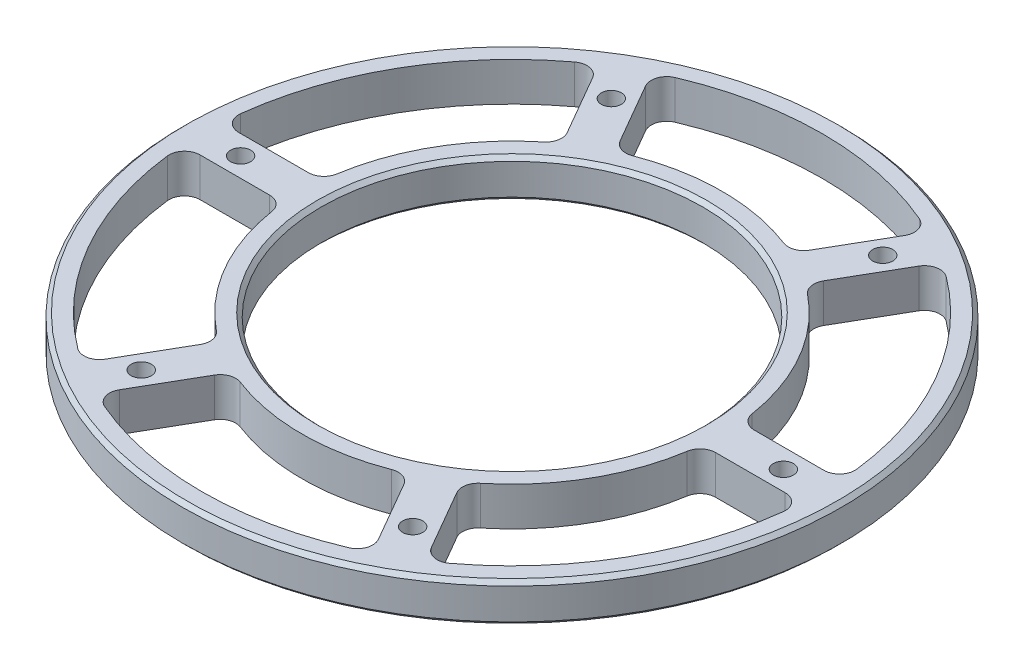
SolidWorks part; units mm, degrees
ref_plane "Front Plane" through (0, 0, 0) normal (0, 0, 1) x (1, 0, 0)
ref_plane "Top Plane" through (0, 0, 0) normal (0, 1, 0) x (1, 0, 0)
ref_plane "Right Plane" through (0, 0, 0) normal (1, 0, 0) x (0, 0, -1)
sketch "Sketch2" plane through (0, 0, 0) normal (1, 0, 0) x (0, 0, -1)
  line L0 (-49.2125, 0) -> (-84.9998, 0)
  line L1 (-84.9998, 0) -> (-84.9998, 10)
  line L2 (-84.9998, 10) -> (-49.2125, 10)
  line L3 (-49.2125, 10) -> (-49.2125, 0)
  dimension "D1" = 84.9998
  dimension "D2" = 10
  dimension "D4" = 49.2125
ref_axis "Axis1" through (0, -0.75, 0) along (0, 1, 0)
revolve "Revolve1" add sketch "Sketch2" angle 360 about axis through (0, -0.75, 0) along (0, 1, 0)
hole_wizard "#6 (0.204) Diameter Hole1" positions "Sketch6" profile "Sketch7" hole size "#6" standard "ANSI Inch" end condition through all
sketch "Sketch6" plane through (0, 10, 0) normal (0, 1, 0) x (1, 0, 0)
  line L0 (0, 0) -> (-69.8201, 120.932) construction
  line L2 (0, 0) -> (0, 109.0908) construction
  point P0 (-35, 60.6218)
  dimension "D1" = 30
  dimension "D2" = 70
sketch "Sketch7" plane through (-35, 10, -60.6218) normal (1, 0, 0) x (0, 0, 1)
  line L0 (0, 0) -> (0, 10)
  line L1 (0, 10) -> (2.5908, 10)
  line L2 (2.5908, 10) -> (2.5908, 0)
  line L5 (2.5908, 0) -> (0, 0)
  line L11 (0, -6.35) -> (0, 107.95) construction
  dimension "Thru Hole Dia." = 5.1816
  dimension "Thru Hole Depth" = 10
pattern_circular "CirPattern3" count 6 over 360 about axis through (0, -0.75, 0) along (0, 1, 0) of "#6 (0.204) Diameter Hole1"
sketch "Sketch8" plane through (0, 10, 0) normal (0, 1, 0) x (1, 0, 0)
  line L4 (0, 0) -> (0, 93.9995) construction
  line L5 (-22.6606, 49.2493) -> (-35.5916, 71.6464)
  line L6 (22.6606, 49.2493) -> (35.5916, 71.6464)
  line L7 (0, 0) -> (-35, 60.6218) construction
  arc A0 (-22.6606, 49.2493) -> (22.6606, 49.2493) centre (0, 0) cw
  arc A1 (-35.5916, 71.6464) -> (35.5916, 71.6464) centre (0, 0) cw
  circle A2 centre (0, 0) radius 84.9998 construction
  circle A4 centre (0, 0) radius 49.2125 construction
  dimension "D1" = 5
  dimension "D2" = 5
  dimension "D3" = 5
extrude "Cut-Extrude1" cut sketch "Sketch8" against normal through all
fillet "Fillet1" radius 4 4 edges at (-22.6606, 5, -49.2493) (22.6606, 5, -49.2493) (35.5916, 5, -71.6464) (-35.5916, 5, -71.6464)
pattern_circular "CirPattern4" count 6 over 360 about axis through (0, -0.75, 0) along (0, 1, 0) of "Cut-Extrude1", "Fillet1"
chamfer "Chamfer1" distance 1 angle 45 2 edges at (0, 10, -49.2125) (0, 0, -49.2125)
chamfer "Chamfer2" distance 1 angle 45 2 edges at (0, 10, -84.9998) (0, 0, -84.9998)
